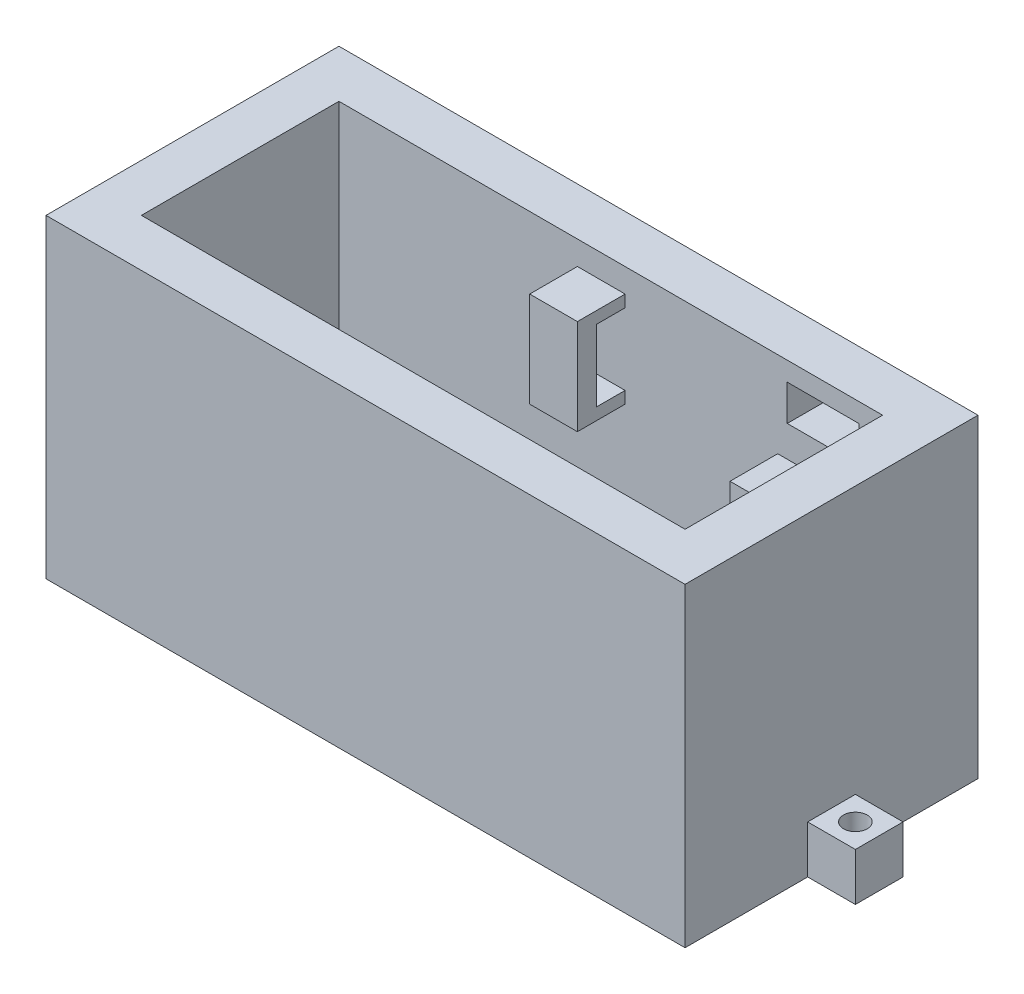
SolidWorks part; units mm, degrees
ref_plane "Front Plane" through (0, 0, 0) normal (0, 0, 1) x (1, 0, 0)
ref_plane "Top Plane" through (0, 0, 0) normal (0, 1, 0) x (1, 0, 0)
ref_plane "Right Plane" through (0, 0, 0) normal (1, 0, 0) x (0, 0, -1)
sketch "Sketch1" plane through (0, 0, 0) normal (0, 1, 0) x (1, 0, 0)
  line L0 (79.6216, 160.5161) -> (399.276, 160.5161) construction
  line L1 (-6.35, 13.1527) -> (-17.8092, 13.1527) construction
  line L2 (3.175, 25.908) -> (28.575, 25.908)
  line L3 (3.175, 25.908) -> (3.175, 0.508)
  line L4 (3.175, 0.508) -> (28.575, 0.508)
  line L5 (28.575, 25.908) -> (28.575, 0.508)
  line L6 (53.975, 25.8098) -> (69.215, 25.8098)
  line L7 (53.975, 25.8098) -> (53.975, 0.4098)
  line L8 (53.975, 0.4098) -> (69.215, 0.4098)
  line L9 (69.215, 25.8098) -> (69.215, 0.4098)
  line L10 (0, 0) -> (72.39, 0)
  line L11 (0, 0) -> (0, 26.3054)
  line L12 (0, 26.3054) -> (72.39, 26.3054)
  line L13 (72.39, 0) -> (72.39, 26.3054)
  line L14 (-6.35, 32.6554) -> (78.74, 32.6554)
  line L15 (-6.35, 32.6554) -> (-6.35, -6.35)
  line L16 (-6.35, -6.35) -> (78.74, -6.35)
  line L17 (78.74, 32.6554) -> (78.74, -6.35)
  line L18 (-6.35, 9.9777) -> (-12.7, 9.9777)
  line L19 (-6.35, 9.9777) -> (-6.35, 16.3277)
  line L20 (-6.35, 16.3277) -> (-12.7, 16.3277)
  line L21 (-12.7, 9.9777) -> (-12.7, 16.3277)
  line L22 (78.74, 16.3277) -> (85.09, 16.3277)
  line L23 (78.74, 16.3277) -> (78.74, 9.9777)
  line L24 (78.74, 9.9777) -> (85.09, 9.9777)
  line L25 (85.09, 16.3277) -> (85.09, 9.9777)
  line L27 (53.1812, 0.4098) -> (50.0062, 0.4098)
  line L28 (53.1812, 0.4098) -> (53.1812, 3.5848)
  line L29 (53.1812, 3.5848) -> (50.0062, 3.5848)
  line L30 (50.0062, 0.4098) -> (50.0062, 3.5848)
  circle A0 centre (61.595, 21.9998) radius 1.905
  circle A1 centre (6.985, 22.098) radius 1.9673
  circle A2 centre (-9.525, 13.1527) radius 1.5875
  circle A3 centre (81.915, 13.1527) radius 1.5875
  circle A4 centre (6.985, 22.098) radius 1.397
  circle A5 centre (61.595, 21.9998) radius 1.397
  dimension "D5" = 3.81
  dimension "D6" = 3.81
  dimension "D8" = 3.9346
  dimension "D9" = 3.81
  dimension "D25" = 3.175
  dimension "D28" = 2.794
  dimension "D29" = 2.794
  dimension "D1" = 25.4
  dimension "D2" = 25.4
  dimension "D3" = 25.4
  dimension "D4" = 15.24
  dimension "D7" = 25.4
  dimension "D10" = 3.81
  dimension "D11" = 7.62
  dimension "D12" = 3.175
  dimension "D13" = 0.508
  dimension "D14" = 0.4098
  dimension "D15" = 26.3054
  dimension "D16" = 3.175
  dimension "D17" = 6.35
  dimension "D18" = 6.35
  dimension "D19" = 6.35
  dimension "D20" = 6.35
  dimension "D21" = 6.35
  dimension "D22" = 6.35
  dimension "D23" = 3.175
  dimension "D24" = 3.175
  dimension "D26" = 3.175
  dimension "D27" = 3.175
  dimension "D30" = 0.7937
  dimension "D31" = 0.4098
  dimension "D32" = 3.175
  dimension "D33" = 3.175
extrude "Boss-Extrude1" add sketch "Sketch1" along normal blind 35.56 contours L17 L14 L15 L16 L13 L10 L11 L12 region at (36.195, 0, -31.7194)
extrude "Boss-Extrude2" add sketch "Sketch1<3>" against normal blind 6.35 contours L17 L14 L15 L16 L13 L10 L11 L12 | L10 L13 L12 L11 L6 L9 L8 L7 L2 L5 L4 L3 | L5 L2 L3 L4 A1 | A0 | L9 L6 L7 L8 A0 region at (16.0458, 0, -13.0372) region at (61.595, 0, -12.84) region at (39.8174, 0, -13.2611) region at (36.195, 0, -31.7194) region at (59.7439, 0, -21.9998)
sketch "Sketch1<3>" plane through (0, 0, 0) normal (0, 1, 0) x (1, 0, 0) same geometry as "Sketch1"
extrude "Boss-Extrude3" add sketch "Sketch1<4>" against normal blind 6.35 contours L21 L18 L15 L20 A2 | L25 L22 L17 L24 A3 region at (-6.4398, 0, -13.1527) region at (81.915, 0, -16.2379)
sketch "Sketch1<4>" plane through (0, 0, 0) normal (0, 1, 0) x (1, 0, 0) same geometry as "Sketch1"
extrude "Boss-Extrude4" add sketch "Sketch1<5>" against normal blind 2.54 contours A1 | A1 region at (5.0734, 0, -22.098)
sketch "Sketch1<5>" plane through (0, 0, 0) normal (0, 1, 0) x (1, 0, 0) same geometry as "Sketch1"
sketch "Sketch2" plane through (0, 0, -26.3054) normal (0, 0, 1) x (1, 0, 0)
  line L0 (0, 35.56) -> (72.39, 35.56) construction
  line L1 (31.75, 32.385) -> (38.1, 32.385)
  line L2 (31.75, 32.385) -> (31.75, 19.685)
  line L3 (31.75, 19.685) -> (38.1, 19.685)
  line L4 (38.1, 32.385) -> (38.1, 19.685)
  line L5 (31.75, 30.7975) -> (38.1, 30.7975)
  line L6 (31.75, 30.7975) -> (31.75, 21.2725)
  line L7 (31.75, 21.2725) -> (38.1, 21.2725)
  line L8 (38.1, 30.7975) -> (38.1, 21.2725)
  dimension "D1" = 12.7
  dimension "D2" = 6.35
  dimension "D3" = 1.5875
  dimension "D4" = 1.5875
  dimension "D5" = 3.175
  dimension "D6" = 31.75
extrude "Boss-Extrude8" add sketch "Sketch2" along normal blind 6.35 contours L7 L2 L3 L4 | L2 L7 L4 L5 | L2 L5 L4 L1 region at (34.925, 31.5913, -26.3054) region at (34.925, 26.035, -26.3054) region at (34.925, 20.4788, -26.3054)
extrude "Cut-Extrude1" cut sketch "Sketch2<4>" along normal blind 3.81 contours L5 L8 L7 L6
sketch "Sketch2<4>" plane through (0, 0, -26.3054) normal (0, 0, 1) x (1, 0, 0) same geometry as "Sketch2"
sketch "Sketch3" plane through (0, 0, 0) normal (0, 0, -1) x (-1, 0, 0)
  line L0 (-72.39, 35.56) -> (-72.39, 0) construction
  line L1 (-72.39, 12.7) -> (-62.865, 12.7)
  line L2 (-72.39, 12.7) -> (-72.39, 17.4625)
  line L3 (-72.39, 17.4625) -> (-62.865, 17.4625)
  line L4 (-62.865, 12.7) -> (-62.865, 17.4625)
  line L5 (0, 0) -> (-72.39, 0) construction
  dimension "D1" = 12.7
  dimension "D2" = 4.7625
  dimension "D3" = 9.525
sketch "Sketch4" plane through (0, 0, 6.35) normal (0, 0, 1) x (1, 0, 0)
  line L1 (13.513, 15.4049) -> (19.863, 15.4049)
  line L2 (13.513, 15.4049) -> (13.513, 2.7049)
  line L3 (13.513, 2.7049) -> (19.863, 2.7049)
  line L4 (19.863, 15.4049) -> (19.863, 2.7049)
  line L5 (13.513, 13.8174) -> (19.863, 13.8174)
  line L6 (13.513, 13.8174) -> (13.513, 4.2924)
  line L7 (13.513, 4.2924) -> (19.863, 4.2924)
  line L8 (19.863, 13.8174) -> (19.863, 4.2924)
  dimension "D1" = 12.7
  dimension "D2" = 6.35
  dimension "D3" = 1.5875
  dimension "D4" = 1.5875
extrude "Cut-Extrude4" cut sketch "Sketch1<10>" against normal through all contours A4 | A5 | A0 | A1 region at (6.985, 0, -22.098)
sketch "Sketch1<10>" plane through (0, 0, 0) normal (0, 1, 0) x (1, 0, 0) same geometry as "Sketch1"
delete or keep bodies "Body-Delete/Keep 1" type delete bodies bodies 115
extrude "Boss-Extrude11" add sketch "Sketch1<11>" along normal blind 2.54 and the other way blind 6.35 contours L30 L27 L28 L29 region at (51.5937, 0, -1.9973)
sketch "Sketch1<11>" plane through (0, 0, 0) normal (0, 1, 0) x (1, 0, 0) same geometry as "Sketch1"
sketch "Sketch6" plane through (72.39, 0, -72.39) normal (-1, 0, 0) x (0, 0, 1)
  line L0 (72.39, 35.56) -> (46.0846, 35.56) construction
  line L1 (53.7046, 31.75) -> (60.0546, 31.75)
  line L2 (53.7046, 31.75) -> (53.7046, 19.05)
  line L3 (53.7046, 19.05) -> (60.0546, 19.05)
  line L4 (60.0546, 31.75) -> (60.0546, 19.05)
  line L5 (53.7046, 30.1625) -> (60.0546, 30.1625)
  line L6 (53.7046, 30.1625) -> (53.7046, 20.6375)
  line L7 (53.7046, 20.6375) -> (60.0546, 20.6375)
  line L8 (60.0546, 30.1625) -> (60.0546, 20.6375)
  line L9 (46.0846, 35.56) -> (46.0846, 0) construction
  dimension "D1" = 12.7
  dimension "D2" = 6.35
  dimension "D3" = 1.5875
  dimension "D4" = 1.5875
  dimension "D5" = 3.81
  dimension "D6" = 7.62
extrude "Boss-Extrude12" add sketch "Sketch6" along normal blind 6.35 contours L2 L7 L4 L5 | L2 L5 L4 L1 | L7 L2 L3 L4 region at (72.39, 30.9563, -15.5104) region at (72.39, 25.4, -15.5104) region at (72.39, 19.8438, -15.5104)
extrude "Cut-Extrude5" cut sketch "Sketch6<8>" along normal blind 3.81 contours L2 L7 L4 L5 region at (72.39, 25.4, -15.5104)
sketch "Sketch6<8>" plane through (72.39, 0, -72.39) normal (-1, 0, 0) x (0, 0, 1) same geometry as "Sketch6"
sketch "Sketch8" plane through (0, 0, -26.3054) normal (0, 0, 1) x (1, 0, 0)
  line L0 (0, 35.56) -> (72.39, 35.56) construction
  line L1 (59.69, 33.02) -> (69.215, 33.02)
  line L2 (59.69, 33.02) -> (59.69, 28.2575)
  line L3 (59.69, 28.2575) -> (69.215, 28.2575)
  line L4 (69.215, 33.02) -> (69.215, 28.2575)
  dimension "D1" = 9.525
  dimension "D2" = 4.7625
  dimension "D3" = 0
  dimension "D4" = 2.54
extrude "Cut-Extrude6" cut sketch "Sketch8" against normal blind 18.542
